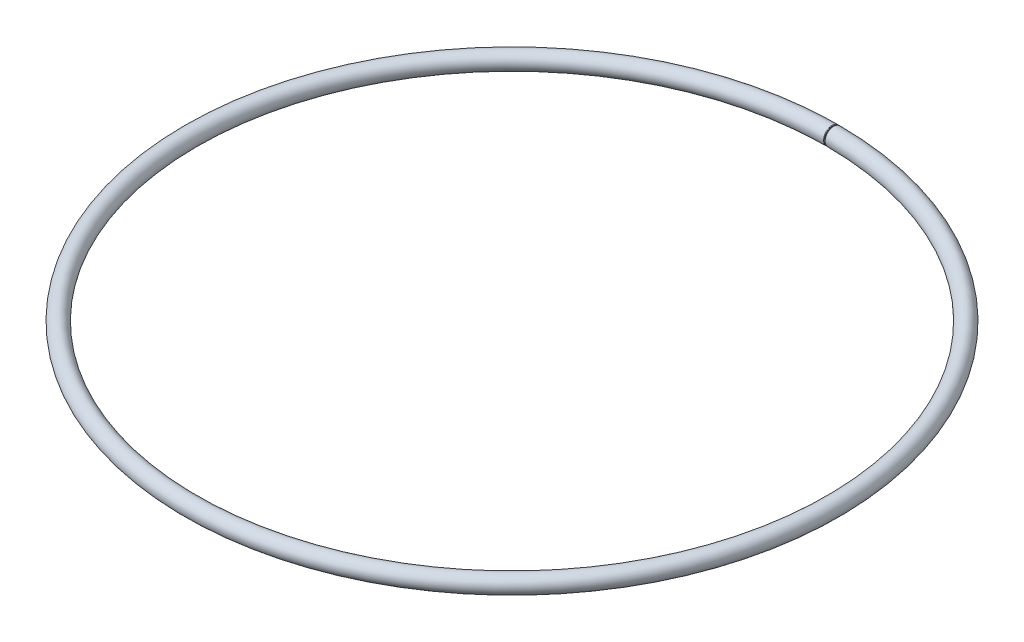
SolidWorks part; units mm, degrees
material "PVC 0.007 Plasticized"
ref_plane "Front Plane" through (0, 0, 0) normal (0, 0, 1) x (1, 0, 0)
ref_plane "Top Plane" through (0, 0, 0) normal (0, 1, 0) x (1, 0, 0)
ref_plane "Right Plane" through (0, 0, 0) normal (1, 0, 0) x (0, 0, -1)
other "hd[e"
sketch "Sketch1" plane through (0, 0, 0) normal (0, 1, 0) x (1, 0, 0)
  circle A0 centre (0, 0) radius 372.5
  dimension "D1" = 745
sketch "Sketch2" plane through (0, 0, 0) normal (1, 0, 0) x (0, 0, -1)
  line L1 (-372.5, 0) -> (0, 0)
  line L2 (0, 0) -> (0, 174.4411) construction
  circle A0 centre (-362.75, 0) radius 9.75
  circle A1 centre (-362.75, 0) radius 8.25
  dimension "D1" = 19.5
  dimension "D2" = 16.5
revolve "Revolve1" add sketch "Sketch2" angle 360 about L2 region at (0, 8.468, 362.75) region at (0, -0.218, 353.75)
sketch "Sketch3" plane through (0, 0, 0) normal (0, 1, 0) x (1, 0, 0)
  line L2 (0, 373.5066) -> (0.5, 373.5066)
  line L3 (0.5, 373.5066) -> (0.5, 352.7296)
  line L4 (0.5, 352.7296) -> (-0.5, 352.7296)
  line L5 (-0.5, 352.7296) -> (-0.5, 373.5066)
  line L6 (-0.5, 373.5066) -> (0, 373.5066)
extrude "Cut-Extrude1" cut sketch "Sketch3" against normal blind 10 and the other way blind 10
fillet "Fillet1" radius 0.5 4 edges at (0.5, 8.307, -357.6451) (-0.5, 5.1426, -354.4662) (0.5, 7.0967, -358.5426) (-0.5, 4.4622, -355.8106)
